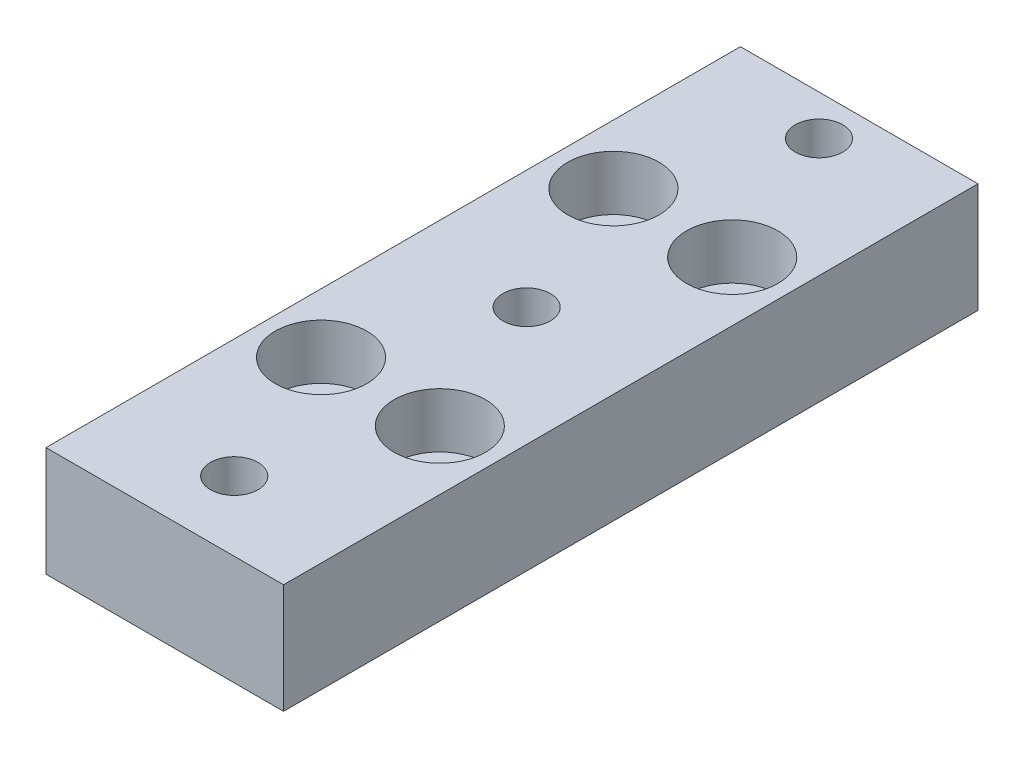
SolidWorks part; units mm, degrees
ref_plane "Front Plane" through (0, 0, 0) normal (0, 0, 1) x (1, 0, 0)
ref_plane "Top Plane" through (0, 0, 0) normal (0, 1, 0) x (1, 0, 0)
ref_plane "Right Plane" through (0, 0, 0) normal (1, 0, 0) x (0, 0, -1)
sketch "Sketch1" plane through (0, 0, 0) normal (0, 1, 0) x (1, 0, 0)
  line L0 (-3.25, -9.5) -> (-3.25, 9.5)
  line L1 (-3.25, -9.5) -> (3.25, -9.5)
  line L2 (-3.25, 9.5) -> (3.25, 9.5)
  line L3 (3.25, -9.5) -> (3.25, 9.5)
  line L4 (-3.25, -9.5) -> (3.25, 9.5) construction
  line L5 (-3.25, 9.5) -> (3.25, -9.5) construction
  point P1 (0, 0)
  dimension "D1" = 19
  dimension "D2" = 6.5
extrude "Boss-Body" add sketch "Sketch1" against normal blind 3
sketch "Sketch2" plane through (0, 0, 0) normal (0, 1, 0) x (1, 0, 0)
  line L0 (0, -1.65) -> (0, 1.65) construction
  line L1 (-3.25, -9.5) -> (3.25, -9.5) construction
  line L2 (0, 8.4) -> (0, 0.4) construction
  line L3 (0, 0.4) -> (0, -7.6) construction
  line L4 (0, 4.4) -> (3.25, 4.4) construction
  line L5 (3.25, -9.5) -> (3.25, 9.5) construction
  line L6 (-3.25, -3.6) -> (0, -3.6) construction
  line L7 (0, 4.4) -> (-3.25, 4.4) construction
  line L8 (-3.25, 9.5) -> (-3.25, -9.5) construction
  line L9 (0, -3.6) -> (3.25, -3.6) construction
  circle A0 centre (0, -7.6) radius 0.65
  circle A1 centre (0, 0.4) radius 0.65
  circle A2 centre (0, 8.4) radius 0.65
  circle A3 centre (1.625, 4.4) radius 0.65
  circle A4 centre (-1.625, -3.6) radius 0.65
  circle A5 centre (-1.625, 4.4) radius 0.65
  circle A6 centre (1.625, -3.6) radius 0.65
  point P22 (0, 4.4)
  point P23 (0, -3.6)
  point P26 (1.625, 4.4)
  point P27 (-1.625, -3.6)
  dimension "D3" = 1.3
  dimension "D4" = 1.9
  dimension "D1" = 8
  dimension "D2" = 8
extrude "Cut-Screw Holes" cut sketch "Sketch2" against normal through all
sketch "Sketch4" plane through (0, 0, 0) normal (0, 1, 0) x (1, 0, 0)
  circle A0 centre (1.625, 4.4) radius 1.25
  circle A1 centre (-1.625, -3.6) radius 1.25
  circle A2 centre (1.625, 4.4) radius 0.65 construction
  circle A3 centre (-1.625, -3.6) radius 0.65 construction
  circle A4 centre (-1.625, 4.4) radius 1.25
  circle A5 centre (1.625, -3.6) radius 1.25
  dimension "D1" = 2.5
extrude "Cut-Screw Head Pockets" cut sketch "Sketch4" against normal blind 1.5
